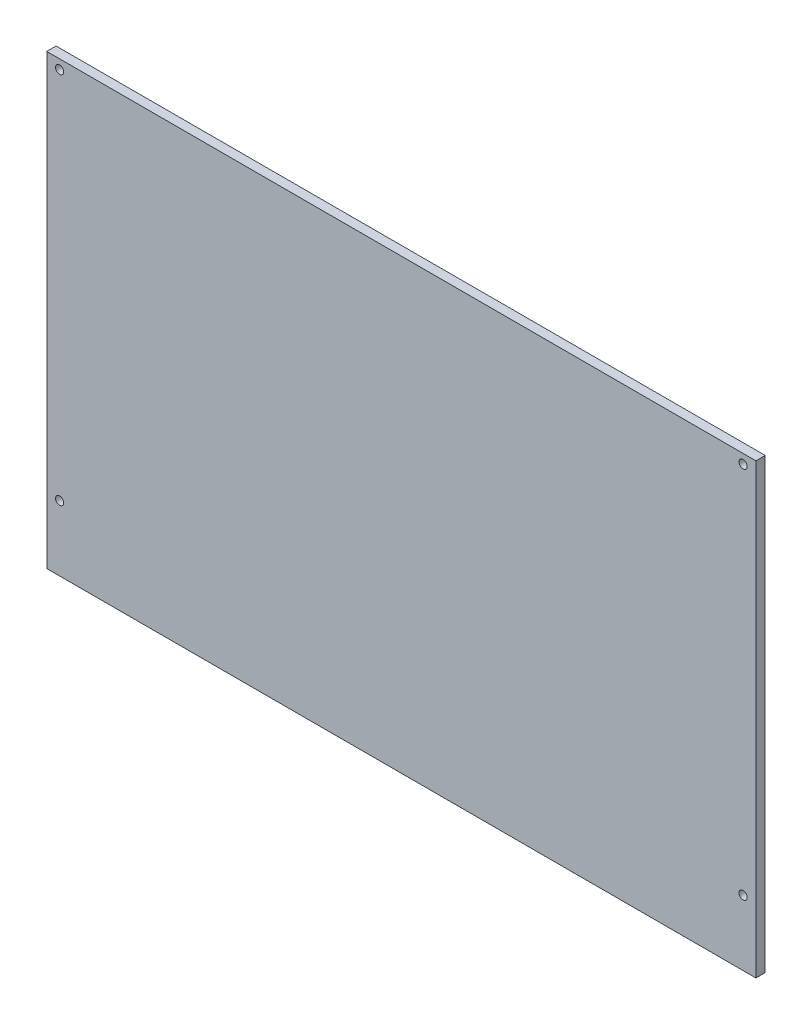
SolidWorks part; units mm, degrees
ref_plane "Front Plane" through (0, 0, 0) normal (0, 0, 1) x (1, 0, 0)
ref_plane "Top Plane" through (0, 0, 0) normal (0, 1, 0) x (1, 0, 0)
ref_plane "Right Plane" through (0, 0, 0) normal (1, 0, 0) x (0, 0, -1)
sketch "Sketch1" plane through (0, 0, 0) normal (0, 0, 1) x (1, 0, 0)
  line L1 (-241.3, -152.4) -> (241.3, -152.4)
  line L2 (-241.3, -152.4) -> (-241.3, 152.4)
  line L3 (-241.3, 152.4) -> (241.3, 152.4)
  line L4 (241.3, -152.4) -> (241.3, 152.4)
  line L5 (-241.3, -152.4) -> (241.3, 152.4) construction
  line L6 (-241.3, 152.4) -> (241.3, -152.4) construction
  point P0 (0, 0)
  dimension "D1" = 482.6
  dimension "D2" = 304.8
extrude "Boss-Extrude1" add sketch "Sketch1" along normal blind 6.35
sketch "Sketch2" plane through (0, 0, 6.35) normal (0, 0, 1) x (1, 0, 0)
  line L0 (-241.3, 0) -> (241.3, 0) construction
  line L1 (-241.3, 152.4) -> (-241.3, -152.4) construction
  line L2 (241.3, -152.4) -> (241.3, 152.4) construction
  line L3 (241.3, 152.4) -> (-241.3, 152.4) construction
  circle A0 centre (-232.5624, 146.05) radius 2.7813
  circle A1 centre (-232.5624, -107.95) radius 2.7813
  point P10 (0, 0)
  dimension "D2" = 5.5626
  dimension "D3" = 5.5626
  dimension "D1" = 8.7376
  dimension "D4" = 6.35
  dimension "D5" = 254
extrude "Cut-Extrude1" cut sketch "Sketch2" against normal through all
mirror "Mirror1" about plane through (0, 0, 0) normal (1, 0, 0) of "Cut-Extrude1"
